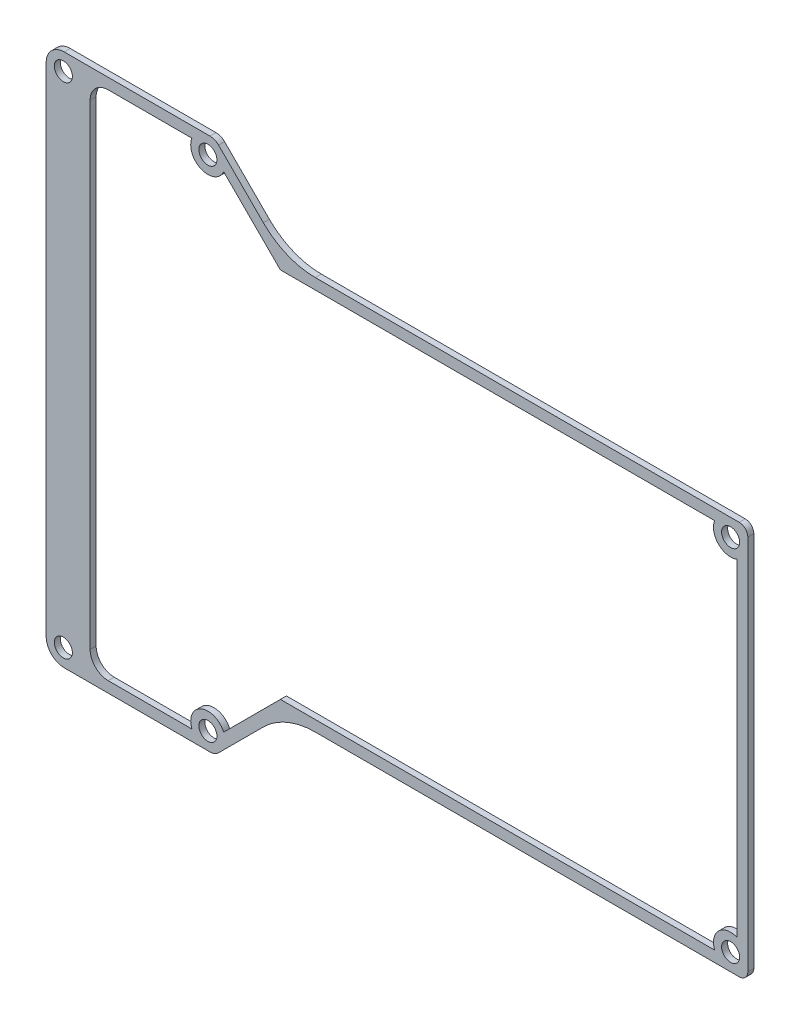
SolidWorks part; units mm, degrees
ref_plane "Front Plane" through (0, 0, 0) normal (0, 0, 1) x (1, 0, 0)
ref_plane "Top Plane" through (0, 0, 0) normal (0, 1, 0) x (1, 0, 0)
ref_plane "Right Plane" through (0, 0, 0) normal (1, 0, 0) x (0, 0, -1)
sketch "Sketch2" plane through (0, 0, 0) normal (0, 0, 1) x (1, 0, 0)
  line L8 (28.7801, -21.4985) -> (21.333, -14.0514)
  line L9 (107.834, -25.0706) -> (37.404, -25.0706)
  line L10 (109.259, -89.0386) -> (109.259, -26.4956)
  line L11 (37.409, -90.4636) -> (107.834, -90.4636)
  line L12 (21.333, -101.4878) -> (28.7851, -94.0357)
  line L13 (-4.3, -102.0736) -> (19.9188, -102.0736)
  line L14 (-7.3, -16.4656) -> (-7.3, -99.0736)
  line L15 (19.9188, -13.4656) -> (-4.3, -13.4656)
  line L24 (16.9123, -100.2696) -> (3, -100.2696)
  line L25 (31.61, -88.6596) -> (22.1833, -98.0863)
  line L26 (103.7528, -88.6596) -> (31.61, -88.6596)
  line L27 (107.455, -84.9574) -> (107.455, -30.5767)
  line L28 (31.605, -26.8746) -> (103.7528, -26.8746)
  line L29 (22.1833, -17.4529) -> (31.605, -26.8746)
  line L30 (0, -97.2696) -> (0, -18.2696)
  line L31 (3, -15.2696) -> (16.9123, -15.2696)
  arc A8 (21.333, -14.0514) -> (19.9188, -13.4656) centre (19.9188, -15.4656) ccw
  arc A9 (28.7801, -21.4985) -> (37.404, -25.0706) centre (37.404, -12.8746) ccw
  arc A10 (109.259, -26.4956) -> (107.834, -25.0706) centre (107.834, -26.4956) ccw
  arc A11 (107.834, -90.4636) -> (109.259, -89.0386) centre (107.834, -89.0386) ccw
  arc A12 (37.409, -90.4636) -> (28.7851, -94.0357) centre (37.409, -102.6596) ccw
  arc A13 (19.9188, -102.0736) -> (21.333, -101.4878) centre (19.9188, -100.0736) ccw
  arc A14 (-7.3, -99.0736) -> (-4.3, -102.0736) centre (-4.3, -99.0736) ccw
  arc A15 (-4.3, -13.4656) -> (-7.3, -16.4656) centre (-4.3, -16.4656) ccw
  arc A23 (0, -97.2696) -> (3, -100.2696) centre (3, -97.2696) ccw
  arc A24 (22.1833, -98.0863) -> (16.9123, -100.2696) centre (19.5655, -99.2206) ccw
  arc A25 (107.455, -84.9574) -> (103.7528, -88.6596) centre (106.406, -87.6106) ccw
  arc A26 (103.7528, -26.8746) -> (107.455, -30.5767) centre (106.406, -27.9236) ccw
  arc A27 (16.9123, -15.2696) -> (22.1833, -17.4529) centre (19.5655, -16.3186) ccw
  arc A28 (3, -15.2696) -> (0, -18.2696) centre (3, -18.2696) ccw
  circle A29 centre (-4.447, -16.3186) radius 1.5
  circle A35 centre (106.406, -87.6106) radius 1.5
  circle A36 centre (106.406, -27.9236) radius 1.5
  circle A37 centre (19.5655, -16.3186) radius 1.5
  circle A38 centre (-4.447, -99.2206) radius 1.5
  circle A39 centre (19.5655, -99.2206) radius 1.5
extrude "Boss-Extrude1" add sketch "Sketch2" along normal blind 1
